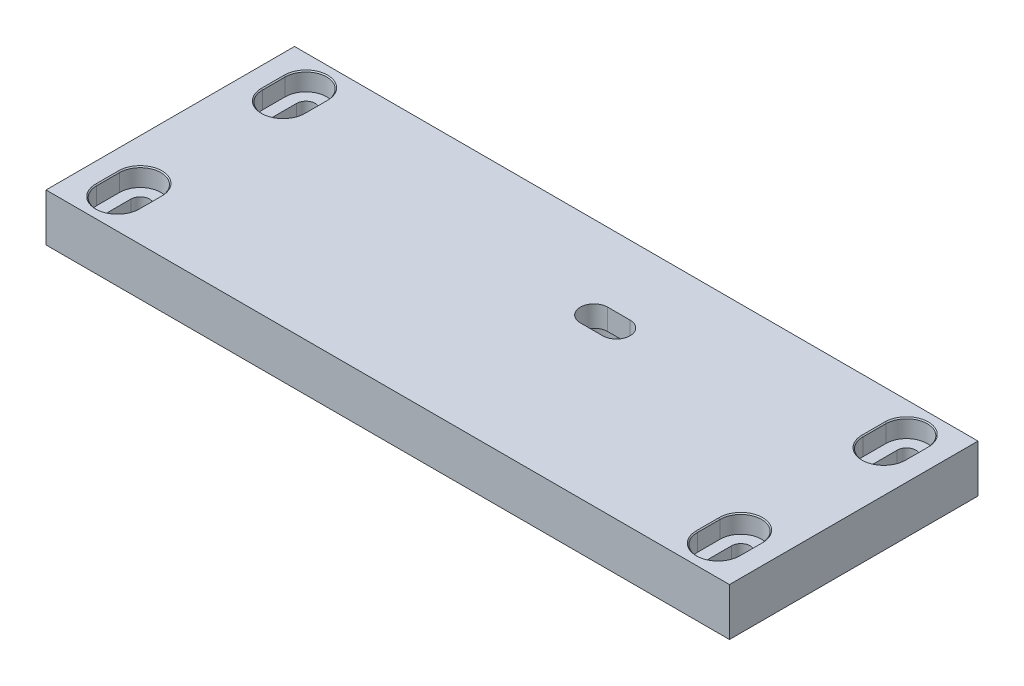
SolidWorks part; units mm, degrees
material "Oak"
ref_plane "Front Plane" through (0, 0, 0) normal (0, 0, 1) x (1, 0, 0)
ref_plane "Top Plane" through (0, 0, 0) normal (0, 1, 0) x (1, 0, 0)
ref_plane "Right Plane" through (0, 0, 0) normal (1, 0, 0) x (0, 0, -1)
sketch "Sketch1" plane through (0, 0, 0) normal (0, 1, 0) x (1, 0, 0)
  line L1 (-82.5, 30) -> (82.5, 30)
  line L2 (-82.5, 30) -> (-82.5, -30)
  line L3 (-82.5, -30) -> (82.5, -30)
  line L4 (82.5, 30) -> (82.5, -30)
  line L5 (-82.5, 30) -> (82.5, -30) construction
  line L6 (-82.5, -30) -> (82.5, 30) construction
  point P0 (0, 0)
  dimension "D1" = 165
  dimension "D2" = 60
extrude "Boss-Extrude1" add sketch "Sketch1" along normal blind 11.5
hole_wizard "CBORE SLOT for M4 Hex Socket Head Cap Screw1" positions "Sketch2" profile "Sketch3" size "M4" standard "DIN" slot yes end condition through all
sketch "Sketch2" plane through (0, 11.5, 0) normal (0, 1, 0) x (1, 0, 0)
  line L1 (0, 42.2454) -> (0, -43.7693) construction
  line L3 (-90.5864, 0) -> (123.9462, 0) construction
  line L5 (-82.5, 30) -> (-82.5, -30) construction
  line L6 (-72.5, 15) -> (-72.5, 25) construction
  point P0 (-72.5, 20)
  point P15 (-72.5, -20)
  point P16 (72.5, -20)
  point P17 (72.5, 20)
  dimension "D1" = 40
  dimension "D2" = 10
  dimension "D3" = 10
sketch "Sketch3" plane through (-72.5, 11.5, -20) normal (1, 0, 0) x (0, 0, 1)
  line L0 (0, 0) -> (0, 11.5)
  line L1 (0, 11.5) -> (2.25, 11.5)
  line L3 (2.25, 11.5) -> (2.25, 4.4)
  line L4 (5, 4.4) -> (2.25, 4.4)
  line L5 (5, 4.4) -> (5, 0.25)
  line L6 (5, 0.25) -> (5.25, 0)
  line L7 (5.25, 0) -> (0, 0)
  line L8 (-5, 0.25) -> (-5.25, 0) construction
  line L11 (0, -6.35) -> (0, 107.95) construction
  dimension "Thru Hole Dia." = 4.5
  dimension "Thru Hole Depth" = 11.5
  dimension "C'Bore Dia." = 10
  dimension "C'Bore Depth" = 4.4
  dimension "Near C'Sink Dia." = 10.5
  dimension "Near C'Sink Angle" = 90
hole_wizard "CBORE SLOT for M6 Hex Socket Head Cap Screw1" positions "Sketch4" profile "Sketch5" size "M6" standard "DIN" slot yes end condition through all
sketch "Sketch4" plane through (0, 0, 0) normal (0, -1, 0) x (-1, 0, 0)
  line L0 (-6.5, 10) -> (-18.5, 10) construction
  point P0 (-12.5, 10)
  dimension "D1" = 12
sketch "Sketch5" plane through (12.5, 0, -10) normal (1, 0, 0) x (0, 0, -1)
  line L0 (0, 0) -> (0, 11.5)
  line L1 (0, 11.5) -> (3.3, 11.5)
  line L3 (3.3, 11.5) -> (3.3, 6.4)
  line L4 (5.5, 6.4) -> (3.3, 6.4)
  line L5 (5.5, 6.4) -> (5.5, 0.025)
  line L6 (5.5, 0.025) -> (5.525, 0)
  line L7 (5.525, 0) -> (0, 0)
  line L8 (-5.5, 0.025) -> (-5.525, 0) construction
  line L11 (0, -6.35) -> (0, 107.95) construction
  dimension "Thru Hole Dia." = 6.6
  dimension "Thru Hole Depth" = 11.5
  dimension "C'Bore Dia." = 11
  dimension "C'Bore Depth" = 6.4
  dimension "Near C'Sink Dia." = 11.05
  dimension "Near C'Sink Angle" = 90
